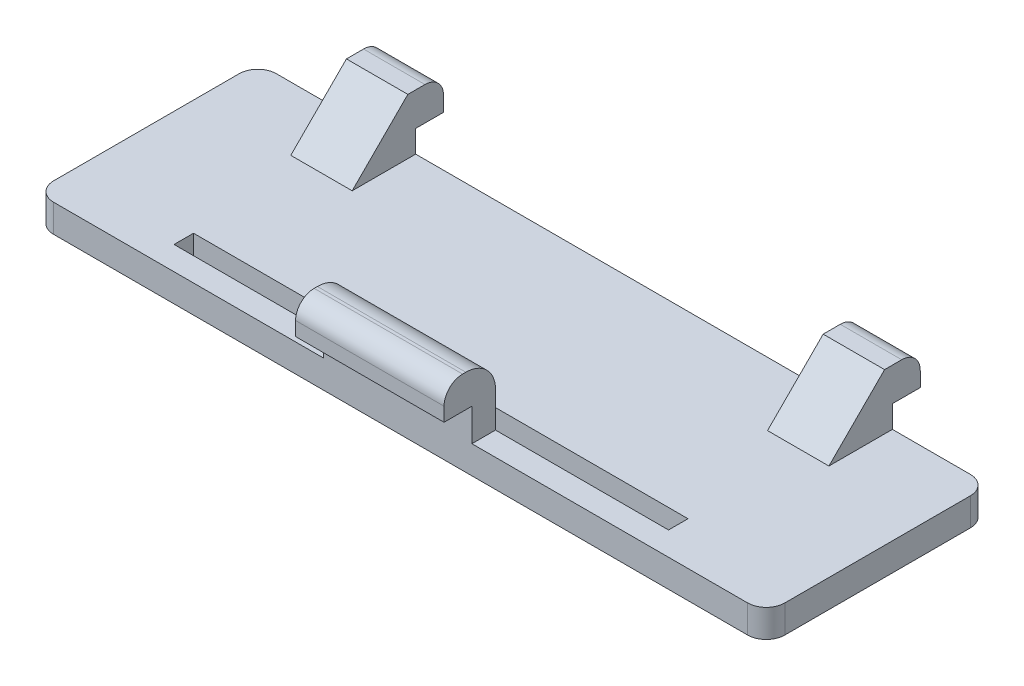
SolidWorks part; units mm, degrees
ref_plane "Front Plane" through (0, 0, 0) normal (0, 0, 1) x (1, 0, 0)
ref_plane "Top Plane" through (0, 0, 0) normal (0, 1, 0) x (1, 0, 0)
ref_plane "Right Plane" through (0, 0, 0) normal (1, 0, 0) x (0, 0, -1)
sketch "Sketch1" plane through (0, 0, 0) normal (0, 1, 0) x (1, 0, 0)
  line L1 (-11.7081, -10.7027) -> (-11.7081, -9.6527)
  line L2 (-17.9227, 0.0241) -> (21.4773, 0.0241)
  line L4 (-17.9227, -11.9759) -> (21.4773, -11.9759)
  line L5 (21.4773, 0.0241) -> (21.4773, -11.9759)
  line L6 (-2.3843, -12) -> (5.6157, -12)
  line L9 (5.6157, -12) -> (5.6157, -10.7027)
  line L11 (12.7773, 0.0241) -> (12.7773, -1.6057)
  line L12 (12.7773, -1.6057) -> (15.7773, -1.6057)
  line L13 (15.7773, 0.0241) -> (15.7773, -1.6057)
  line L14 (-11.7081, -10.7027) -> (14.9394, -10.7027)
  line L16 (-11.7081, -9.6527) -> (14.9394, -9.6527)
  line L17 (14.9394, -10.7027) -> (14.9394, -9.6527)
  line L18 (-12.2683, -0.0672) -> (-12.2683, -1.6729)
  line L19 (-9.2683, -1.6729) -> (-12.2683, -1.6729)
  line L20 (-9.2683, -0.0672) -> (-9.2683, -1.6729)
  line L21 (-9.2683, -0.0672) -> (-12.2683, -0.0672)
  line L22 (-2.3843, -12) -> (-2.3843, -10.7027)
  line L23 (-17.9227, 0.0241) -> (-17.9227, -11.9759)
  line L24 (-2.3843, -10.7027) -> (5.6157, -10.7027)
  line L25 (-2.3843, -10.7027) -> (-2.3843, -12)
  line L26 (-2.3843, -12) -> (5.6157, -12)
  line L27 (5.6157, -10.7027) -> (5.6157, -12)
  dimension "D1" = 12
  dimension "D4" = 5.7
  dimension "D5" = 3
extrude "Boss-Extrude21" add sketch "Sketch1" along normal blind 1.5 contours L13 L2 L11 L12 | L20 L21 L18 L19 | L2 L23 L4 L22 L14 L1 L16 L17 L9 L5 L13 L12 L11 L21 L20 L19 L18
sketch "Sketch3" plane through (-2.3843, 0, 0) normal (1, 0, 0) x (0, 0, -1)
  line L1 (-5.0789, 0.1555) -> (-4.6249, 0.1555)
  line L2 (-5.0789, 0.1555) -> (-5.0789, -0.88)
  line L3 (-5.0789, -0.88) -> (-4.6249, -0.88)
  line L4 (-4.6249, 0.1555) -> (-4.6249, -0.88)
sketch "Sketch4" plane through (0, 0, 0) normal (0, -1, 0) x (1, 0, 0)
  line L1 (5.6157, 10.7027) -> (14.9394, 10.7027) construction
  line L2 (-2.3843, 11.9759) -> (5.6157, 11.9759)
  line L3 (-2.3843, 11.9759) -> (-2.3843, 10.7027)
  line L4 (-2.3843, 10.7027) -> (5.6157, 10.7027)
  line L5 (5.6157, 11.9759) -> (5.6157, 10.7027)
extrude "Boss-Extrude22" add sketch "Sketch4" along normal blind 0.0001 and the other way blind 5
sketch "Sketch5" plane through (0, 0, 11.9759) normal (0, 0, 1) x (1, 0, 0)
  line L0 (5.6157, 5) -> (5.6157, 1.5) construction
  line L1 (5.6157, 5) -> (-2.3843, 5)
  line L2 (5.6157, 5) -> (5.6157, 3.25)
  line L3 (5.6157, 3.25) -> (-2.3843, 3.25)
  line L4 (-2.3843, 5) -> (-2.3843, 3.25)
  line L5 (5.6157, 5) -> (-2.3843, 5) construction
  line L6 (-2.3843, 5) -> (-2.3843, 1.5) construction
extrude "Boss-Extrude23" add sketch "Sketch5" along normal blind 1.5 contours L2 L1 L4 L3
sketch "Sketch6" plane through (0, 1.5, 0) normal (0, 1, 0) x (1, 0, 0)
  line L0 (-17.9227, 0.0241) -> (21.4773, 0.0241) construction
  line L1 (12.9676, 0.0241) -> (16.2773, 0.0241)
  line L2 (12.9676, 0.0241) -> (12.9676, -3.398)
  line L3 (12.9676, -3.398) -> (16.2773, -3.398)
  line L4 (16.2773, 0.0241) -> (16.2773, -3.398)
  line L5 (1.7773, 0.0241) -> (1.7773, -17.0309) construction
  line L6 (-12.7227, 0.0241) -> (-12.7227, -3.398)
  line L7 (-9.4129, -3.398) -> (-12.7227, -3.398)
  line L8 (-9.4129, 0.0241) -> (-9.4129, -3.398)
  line L9 (-9.4129, 0.0241) -> (-12.7227, 0.0241)
  line L10 (-17.9227, 0.0241) -> (-17.9227, -11.9759) construction
  dimension "D1" = 5.2
  dimension "D2" = 3.3097
  dimension "D3" = 5.2
extrude "Boss-Extrude24" add sketch "Sketch6" along normal blind 3
sketch "Sketch7" plane through (0, 0, -0.0241) normal (0, 0, -1) x (-1, 0, 0)
  line L0 (-12.9676, 4.5) -> (-12.9676, 1.5) construction
  line L1 (-16.2773, 4.5) -> (-12.9676, 4.5)
  line L2 (-16.2773, 4.5) -> (-16.2773, 2.7)
  line L3 (-16.2773, 2.7) -> (-12.9676, 2.7)
  line L4 (-12.9676, 4.5) -> (-12.9676, 2.7)
  line L5 (12.7227, 4.5) -> (12.7227, 1.5) construction
  line L6 (9.4129, 4.5) -> (12.7227, 4.5)
  line L7 (9.4129, 4.5) -> (9.4129, 2.3983)
  line L9 (12.7227, 4.5) -> (12.7227, 2.3983)
  line L10 (17.9227, 0) -> (-21.4773, 0) construction
  line L12 (9.4129, 4.5) -> (12.7227, 4.5)
  line L13 (9.4129, 4.5) -> (9.4129, 2.7)
  line L14 (9.4129, 2.7) -> (12.7227, 2.7)
  line L15 (12.7227, 4.5) -> (12.7227, 2.7)
  dimension "D1" = 2.7
sketch "Sketch8" plane through (0, 0, -0.0241) normal (0, 0, -1) x (-1, 0, 0)
  line L0 (-12.9676, 4.5) -> (-12.9676, 1.5) construction
  line L1 (-16.2773, 4.5) -> (-12.9676, 4.5)
  line L2 (-16.2773, 4.5) -> (-16.2773, 2.7)
  line L3 (-16.2773, 2.7) -> (-12.9676, 2.7)
  line L4 (-12.9676, 4.5) -> (-12.9676, 2.7)
  line L5 (17.9227, 0) -> (-21.4773, 0) construction
  line L6 (12.7227, 4.5) -> (12.7227, 1.5) construction
  line L7 (9.4129, 4.5) -> (12.7227, 4.5)
  line L8 (9.4129, 4.5) -> (9.4129, 2.7)
  line L9 (9.4129, 2.7) -> (12.7227, 2.7)
  line L10 (12.7227, 4.5) -> (12.7227, 2.7)
  line M16 (-12.9676, 1.5) -> (-12.9676, 4.5)
  line M17 (-12.9676, 4.5) -> (-16.2773, 4.5)
  line M18 (-16.2773, 4.5) -> (-16.2773, 1.5)
  dimension "D1" = 2.7
extrude "Boss-Extrude26" add sketch "Sketch8" along normal blind 1.5 contours L3 M18 M16 M17 | L8 L7 L10 L9 region at (14.6225, 3.6, -0.0241)
fillet "Fillet1" radius 1 3 edges at (1.6157, 5, 13.4759) (-11.0678, 4.5, -1.5241) (14.6225, 4.5, -1.5241)
fillet "Fillet2" radius 1 4 edges at (21.4773, 0.75, -0.0241) (21.4773, 0.75, 11.9759) (-17.9227, 0.75, 11.9759) (-17.9227, 0.75, -0.0241)
chamfer "Chamfer4" distance 3 angle 45 2 edges at (14.6225, 4.5, 3.398) (-11.0678, 4.5, 3.398)
fillet "Fillet3" radius 1.6 1 edges at (1.6157, 5, 10.7027)
